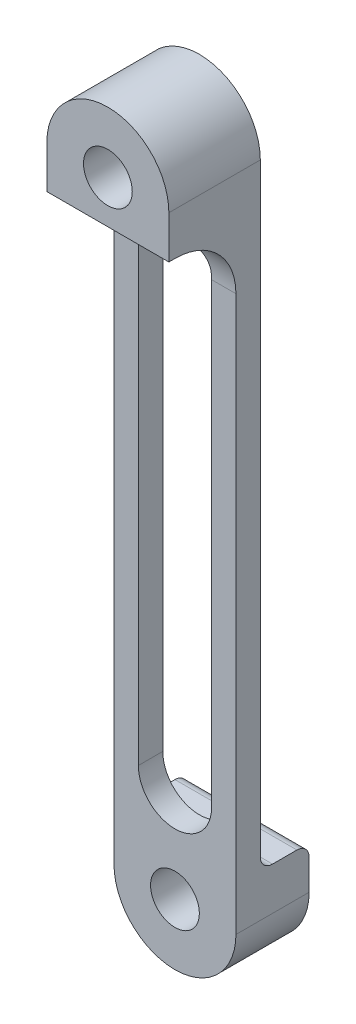
SolidWorks part; units mm, degrees
material "PLA"
ref_plane "Alzado" through (0, 0, 0) normal (0, 0, 1) x (1, 0, 0)
ref_plane "Planta" through (0, 0, 0) normal (0, 1, 0) x (1, 0, 0)
ref_plane "Vista lateral" through (0, 0, 0) normal (1, 0, 0) x (0, 0, -1)
sketch "Croquis1" plane through (0, 0, 0) normal (0, 0, 1) x (1, 0, 0)
  line L0 (0, 54) -> (0, -54) construction
  line L1 (10, 54) -> (10, -54)
  line L2 (-10, 54) -> (-10, -54)
  line L3 (0, 38) -> (0, -38) construction
  line L4 (6, 38) -> (6, -38)
  line L5 (-6, 38) -> (-6, -38)
  line L6 (-10, -47) -> (10, -47)
  line L7 (0, 50) -> (0, 44) construction
  line L8 (-10, 47) -> (10, 47)
  line L9 (0, -50) -> (0, -44) construction
  arc A0 (10, 54) -> (-10, 54) centre (0, 54) ccw
  arc A1 (-10, -54) -> (10, -54) centre (0, -54) ccw
  circle A2 centre (0, 54) radius 4
  circle A3 centre (0, -54) radius 4
  arc A4 (6, 38) -> (-6, 38) centre (0, 38) ccw
  arc A5 (-6, -38) -> (6, -38) centre (0, -38) ccw
  point P2 (0, 0)
  point P14 (0, 0)
  point P23 (0, 47)
  point P28 (0, -47)
  dimension "D1" = 8
  dimension "D2" = 20
  dimension "D3" = 108
  dimension "D4" = 4
  dimension "D5" = 16
extrude "Saliente-Extruir1" add sketch "Croquis1" along normal blind 4 contours L1 A0 L2 L8 A2 | L2 A1 L1 L8 A5 L5 A4 L4 A3 | L2 A1 L1 A0 | A3 | L5 A5 L4 A4 region at (9.7375, 50.5, 0) region at (9.039, 0, 0)
extrude "Saliente-Extruir2" add sketch "Croquis1<5>" against normal blind 8 contours L2 A1 L1 L6 A3 region at (9.7375, -50.5, 0)
sketch "Croquis1<5>" plane through (0, 0, 0) normal (0, 0, 1) x (1, 0, 0) same geometry as "Croquis1"
fillet "Redondeo2" radius 2 2 edges at (0, -47, -8) (0, -47, 0)
extrude "Saliente-Extruir3" add sketch "Croquis1<6>" along normal blind 15 contours L1 A0 L2 L8 A2 region at (9.7375, 50.5, 0)
sketch "Croquis1<6>" plane through (0, 0, 0) normal (0, 0, 1) x (1, 0, 0) same geometry as "Croquis1"
fillet "Redondeo1" radius 10 1 edges at (0, 47, 4)
